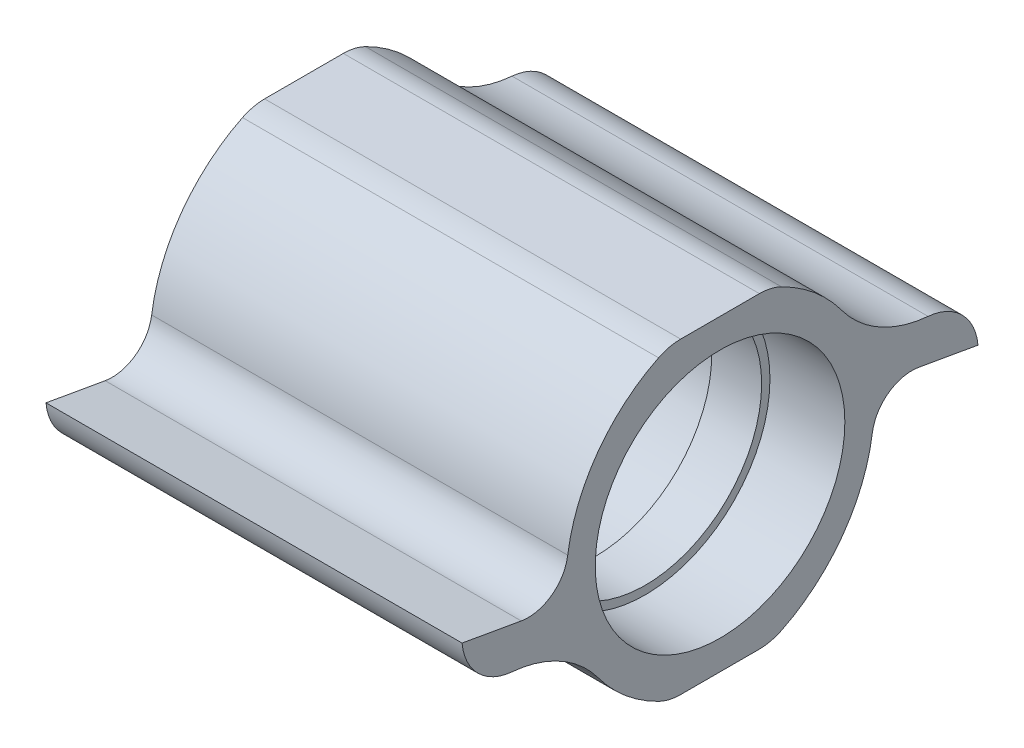
SolidWorks part; units mm, degrees
material "AISI 4340 Steel, annealed"
ref_plane "Front Plane" through (0, 0, 0) normal (0, 0, 1) x (1, 0, 0)
ref_plane "Top Plane" through (0, 0, 0) normal (0, 1, 0) x (1, 0, 0)
ref_plane "Right Plane" through (0, 0, 0) normal (1, 0, 0) x (0, 0, -1)
other "Center of Mass"
ref_axis "Axis1" through (-27.5, 0, 0) along (1, 0, 0)
sketch "Sketch1" plane through (0, 0, 0) normal (1, 0, 0) x (0, 0, -1)
  line L3 (-31, 0) -> (31, 0) construction
  line L4 (-31, 0) -> (-18.3654, -2.2278)
  line L6 (-18.5, 0) -> (18.5, 0)
  line L7 (6, -18.5) -> (-6, -18.5)
  line L9 (0, -18.5) -> (0, 0) construction
  line L12 (31, -18.5) -> (-31, -18.5) construction
  line L13 (31, -18.5) -> (31, 18.5) construction
  line L14 (31, 18.5) -> (-31, 18.5) construction
  line L15 (-31, -18.5) -> (-31, 18.5) construction
  line L16 (31, -18.5) -> (-31, 18.5) construction
  line L17 (31, 18.5) -> (-31, -18.5) construction
  line L18 (-32.335, 15.2593) -> (-30.709, -3.3256) construction
  line L19 (-29.943, -5.5675) -> (-8.3245, -7.4589) construction
  circle A4 centre (0, 0) radius 31 construction
  circle A5 centre (0, 0) radius 18.5 construction
  arc A7 (-18.3654, -2.2278) -> (-18.5, 0) centre (0, 0) cw
  arc A10 (18.5, 0) -> (6, -18.5) centre (-1.44, 0) cw
  arc A11 (-31, 0) -> (-25, -6) centre (-24.4247, 0.5753) ccw
  arc A12 (-25, -6) -> (-14.611, -11.8309) centre (-26.2614, -20.4181) cw
  arc A14 (-6, -18.5) -> (-14.611, -11.8309) centre (1.44, 0) cw
  dimension "D1" = 62
  dimension "D3" = 37
  dimension "D6" = 5
  dimension "D7" = 5
  dimension "D4" = 37
  dimension "D8" = 6
  dimension "D2" = 10
  dimension "D5" = 12
extrude "Boss-Extrude1" add sketch "Sketch1" along normal mid plane 50
fillet "Fillet2" radius 6 2 edges at (0, -18.5, -6) (0, -18.5, 6)
pattern_circular "CirPattern1" count 2 over 360 about axis through (-27.5, 0, 0) along (1, 0, 0) of "Boss-Extrude1", "Fillet2"
fillet "Fillet1" radius 4.8 2 edges at (0, 2.2278, -18.3654) (0, -2.2278, 18.3654)
sketch "Sketch4" plane through (25, 0, 0) normal (1, 0, 0) x (0, 0, -1)
  circle A0 centre (0, 0) radius 14
  dimension "D1" = 28
extrude "Cut-Extrude1" cut sketch "Sketch4" against normal through all
sketch "Sketch5" plane through (-25, 0, 0) normal (-1, 0, 0) x (0, 0, 1)
  circle A0 centre (0, 0) radius 17.5
  circle A1 centre (0, 0) radius 14 construction
  dimension "D1" = 35
extrude "Cut-Extrude2" cut sketch "Sketch5" against normal blind 25
sketch "Sketch6" plane through (0, 0, 0) normal (-1, 0, 0) x (0, 0, 1)
  circle A0 centre (0, 0) radius 15
  circle A1 centre (0, 0) radius 14 construction
  dimension "D1" = 30
extrude "Cut-Extrude3" cut sketch "Sketch6" against normal blind 10
sketch "Sketch7" plane through (25, 0, 0) normal (1, 0, 0) x (0, 0, -1)
  circle A0 centre (0, 0) radius 15
  circle A1 centre (0, 0) radius 14 construction
  dimension "D1" = 30
extrude "Cut-Extrude4" cut sketch "Sketch7" against normal blind 9
